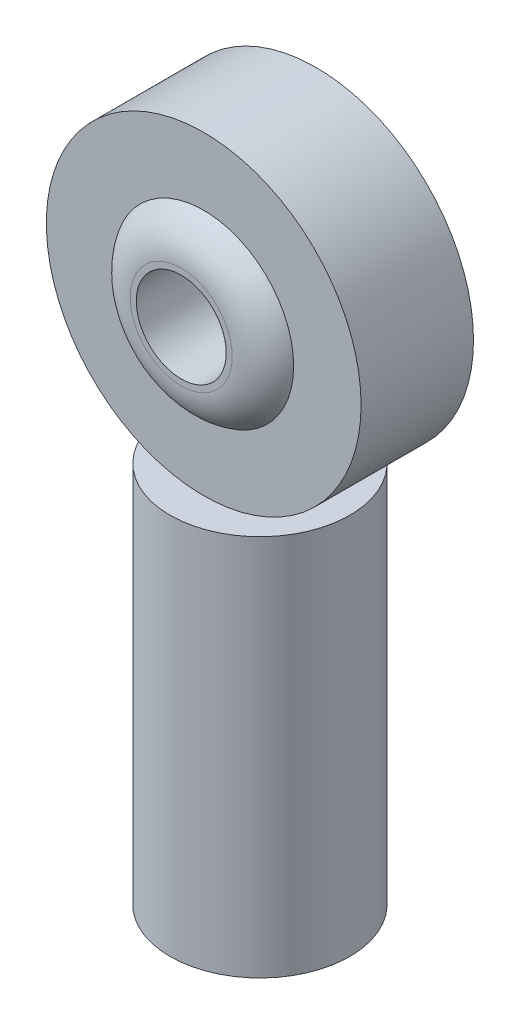
SolidWorks part; units mm, degrees
material "3.1355 (EN-AW 2024)"
ref_plane "Спереди" through (0, 0, 0) normal (0, 0, 1) x (1, 0, 0)
ref_plane "Сверху" through (0, 0, 0) normal (0, 1, 0) x (1, 0, 0)
ref_plane "Справа" through (0, 0, 0) normal (1, 0, 0) x (0, 0, -1)
sketch "Эскиз1" plane through (0, 0, 0) normal (0, 0, 1) x (1, 0, 0)
  circle A0 centre (0, 0) radius 7
  dimension "D1" = 14
extrude "Бобышка-Вытянуть1" add sketch "Эскиз1" along normal blind 2.5 and the other way blind 2.5
sketch3d "Трехмерный эскиз2" plane through (0, 0, 0) normal (0, 0, 1) x (1, 0, 0)
  dimension "D1" = 7
sketch "Эскиз4" plane through (0, -7, 0) normal (0, 1, 0) x (1, 0, 0)
  circle A0 centre (0, 0) radius 4
  dimension "D1" = 8
extrude "Бобышка-Вытянуть2" add sketch "Эскиз4" against normal blind 17 separate body
sketch "Эскиз5" plane through (0, -24, 0) normal (0, -1, 0) x (1, 0, 0)
  circle A0 centre (0, 0) radius 2
  dimension "D1" = 4
extrude "Вырез-Вытянуть1" cut sketch "Эскиз5" against normal blind 12
sketch "Эскиз7" plane through (0, 0, 0) normal (0, 0, 1) x (1, 0, 0)
  circle A0 centre (0, 0) radius 4
  dimension "D1" = 8
extrude "Бобышка-Вытянуть3" add sketch "Эскиз7" along normal blind 3.5 and the other way blind 3.5
sketch "Эскиз8" plane through (0, 0, 3.5) normal (0, 0, 1) x (1, 0, 0)
  circle A0 centre (0, 0) radius 2
  dimension "D1" = 4
extrude "Вырез-Вытянуть2" cut sketch "Эскиз8" against normal through all
fillet "Скругление2" radius 2 2 edges at (4, 0, -3.5) (4, 0, 3.5)
